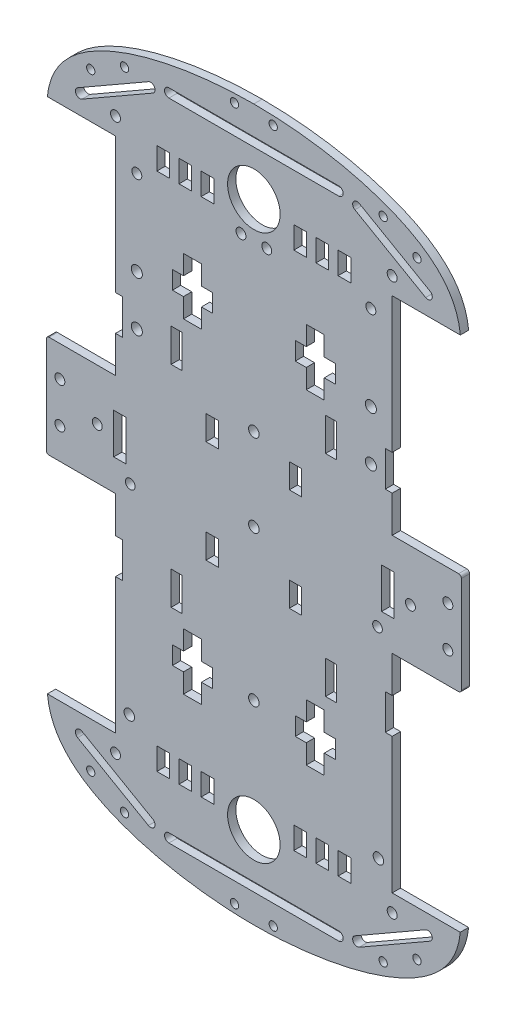
SolidWorks part; units mm, degrees
ref_plane "Plano frontal" through (0, 0, 0) normal (0, 0, 1) x (1, 0, 0)
ref_plane "Plano superior" through (0, 0, 0) normal (0, 1, 0) x (1, 0, 0)
ref_plane "Plano direito" through (0, 0, 0) normal (1, 0, 0) x (0, 0, -1)
sketch "Esboço1" plane through (0, 0, 0) normal (0, 0, 1) x (1, 0, 0)
  line L11 (217.8534, 118.1902) -> (156.4555, 118.1902)
  line L12 (156.4555, 114.9902) -> (217.8534, 114.9902)
  line L22 (125.058, 98.9462) -> (150.6447, 113.6322)
  line L23 (149.0517, 116.4076) -> (123.4651, 101.7215)
  line L52 (250.0473, -100.3339) -> (224.4607, -115.0199) construction
  line L53 (249.2509, -98.9462) -> (223.6642, -113.6322)
  line L54 (250.8438, -101.7215) -> (225.2572, -116.4076)
  line L55 (179.2694, -114.9902) -> (187.1544, -128.5) construction
  line L56 (222.205, -97.9605) -> (217.605, -97.9605)
  line L57 (222.205, -97.9605) -> (222.205, -89.9605)
  line L58 (222.205, -89.9605) -> (217.605, -89.9605)
  line L59 (217.605, -97.9605) -> (217.605, -89.9605)
  line L60 (214.205, -89.9605) -> (209.605, -89.9605)
  line L61 (214.205, -89.9605) -> (214.205, -97.9605)
  line L62 (214.205, -97.9605) -> (209.605, -97.9605)
  line L63 (209.605, -89.9605) -> (209.605, -97.9605)
  line L64 (206.205, -97.9605) -> (201.605, -97.9605)
  line L65 (206.205, -97.9605) -> (206.205, -89.9605)
  line L66 (206.205, -89.9605) -> (201.605, -89.9605)
  line L67 (201.605, -97.9605) -> (201.605, -89.9605)
  line L68 (206.0961, -68.9834) -> (212.5961, -68.9834)
  line L69 (206.0961, -68.9834) -> (206.0961, -48.4834)
  line L70 (206.0961, -48.4834) -> (212.5961, -48.4834)
  line L71 (212.5961, -68.9834) -> (212.5961, -48.4834)
  line L72 (202.1292, -55.4834) -> (216.5834, -55.4834)
  line L73 (202.1292, -55.4834) -> (202.1292, -61.9834)
  line L74 (202.1292, -61.9834) -> (216.5834, -61.9834)
  line L75 (216.5834, -55.4834) -> (216.5834, -61.9834)
  line L76 (213.0509, -44.0251) -> (217.0509, -44.0251)
  line L77 (213.0509, -44.0251) -> (213.0509, -32.0251)
  line L78 (213.0509, -32.0251) -> (217.0509, -32.0251)
  line L79 (217.0509, -44.0251) -> (217.0509, -32.0251)
  line L80 (199.9648, -22.9668) -> (204.4648, -22.9668)
  line L81 (199.9648, -22.9668) -> (199.9648, -14.1027)
  line L112 (137.1544, 44.4469) -> (139.6544, 44.4469)
  line L113 (139.6544, 44.4469) -> (139.6544, 31.679)
  line L114 (139.6544, 31.679) -> (137.1544, 31.679)
  line L115 (137.1544, 31.679) -> (137.1544, 18.463)
  line L116 (137.1544, 18.463) -> (113.1544, 18.463)
  line L117 (112.1544, 17.463) -> (112.1544, -17.463)
  line L118 (113.1544, -18.463) -> (137.1544, -18.463)
  line L119 (137.1544, -18.463) -> (137.1544, -31.679)
  line L120 (137.1544, -31.679) -> (139.6544, -31.679)
  line L121 (139.6544, -31.679) -> (139.6544, -44.4469)
  line L122 (139.6544, -44.4469) -> (137.1544, -44.4469)
  line L123 (137.1544, -44.4469) -> (137.1544, -93.463)
  line L124 (137.1544, -93.463) -> (112.5426, -93.463)
  line L125 (261.7663, -93.463) -> (237.1544, -93.463)
  line L126 (237.1544, -93.463) -> (237.1544, -44.4469)
  line L127 (237.1544, -44.4469) -> (234.6544, -44.4469)
  line L128 (234.6544, -44.4469) -> (234.6544, -31.679)
  line L129 (234.6544, -31.679) -> (237.1544, -31.679)
  line L130 (237.1544, -31.679) -> (237.1544, -18.463)
  line L131 (237.1544, -18.463) -> (261.1544, -18.463)
  line L132 (262.1544, -17.463) -> (262.1544, 17.463)
  line L133 (261.1544, 18.463) -> (237.1544, 18.463)
  line L134 (237.1544, 18.463) -> (237.1544, 31.679)
  line L135 (237.1544, 31.679) -> (234.6544, 31.679)
  line L136 (234.6544, 31.679) -> (234.6544, 44.4469)
  line L137 (234.6544, 44.4469) -> (237.1544, 44.4469)
  line L138 (237.1544, 44.4469) -> (237.1544, 93.463)
  line L139 (237.1544, 93.463) -> (261.7663, 93.463)
  line L140 (112.5426, 93.463) -> (137.1544, 93.463)
  line L141 (137.1544, 93.463) -> (137.1544, 44.4469)
  line L142 (199.9648, -14.1027) -> (204.4648, -14.1027)
  line L143 (204.4648, -22.9668) -> (204.4648, -14.1027)
  line L144 (233.296, -7.3) -> (237.796, -7.3)
  line L145 (201.605, -89.9605) -> (201.605, -97.9605)
  line L146 (206.205, -97.9605) -> (201.605, -97.9605)
  line L147 (206.205, -89.9605) -> (206.205, -97.9605)
  line L148 (206.205, -89.9605) -> (201.605, -89.9605)
  line L149 (209.605, -97.9605) -> (209.605, -89.9605)
  line L150 (214.205, -89.9605) -> (209.605, -89.9605)
  line L151 (214.205, -97.9605) -> (214.205, -89.9605)
  line L152 (214.205, -97.9605) -> (209.605, -97.9605)
  line L153 (217.605, -89.9605) -> (217.605, -97.9605)
  line L154 (222.205, -97.9605) -> (217.605, -97.9605)
  line L155 (222.205, -89.9605) -> (222.205, -97.9605)
  line L156 (222.205, -89.9605) -> (217.605, -89.9605)
  line L157 (237.796, 7.3) -> (237.796, -7.3)
  line L158 (233.296, -7.3) -> (237.796, -7.3)
  line L159 (233.296, 7.3) -> (233.296, -7.3)
  line L160 (233.296, 7.3) -> (237.796, 7.3)
  line L161 (204.4648, 22.9668) -> (204.4648, 14.1027)
  line L162 (199.9648, 14.1027) -> (204.4648, 14.1027)
  line L163 (199.9648, 22.9668) -> (199.9648, 14.1027)
  line L164 (199.9648, 22.9668) -> (204.4648, 22.9668)
  line L165 (217.0509, 44.0251) -> (217.0509, 32.0251)
  line L166 (213.0509, 32.0251) -> (217.0509, 32.0251)
  line L167 (213.0509, 44.0251) -> (213.0509, 32.0251)
  line L168 (213.0509, 44.0251) -> (217.0509, 44.0251)
  line L169 (216.5834, 55.4834) -> (216.5834, 61.9834)
  line L170 (202.1292, 61.9834) -> (216.5834, 61.9834)
  line L171 (202.1292, 55.4834) -> (202.1292, 61.9834)
  line L172 (202.1292, 55.4834) -> (216.5834, 55.4834)
  line L173 (212.5961, 68.9834) -> (212.5961, 48.4834)
  line L174 (206.0961, 48.4834) -> (212.5961, 48.4834)
  line L175 (206.0961, 68.9834) -> (206.0961, 48.4834)
  line L176 (206.0961, 68.9834) -> (212.5961, 68.9834)
  line L177 (201.605, 97.9605) -> (201.605, 89.9605)
  line L178 (206.205, 89.9605) -> (201.605, 89.9605)
  line L179 (206.205, 97.9605) -> (206.205, 89.9605)
  line L180 (206.205, 97.9605) -> (201.605, 97.9605)
  line L181 (209.605, 89.9605) -> (209.605, 97.9605)
  line L182 (214.205, 97.9605) -> (209.605, 97.9605)
  line L183 (214.205, 89.9605) -> (214.205, 97.9605)
  line L184 (214.205, 89.9605) -> (209.605, 89.9605)
  line L185 (217.605, 97.9605) -> (217.605, 89.9605)
  line L186 (222.205, 89.9605) -> (217.605, 89.9605)
  line L187 (222.205, 97.9605) -> (222.205, 89.9605)
  line L188 (222.205, 97.9605) -> (217.605, 97.9605)
  line L189 (237.1544, 93.463) -> (237.1544, 44.4469)
  line L190 (261.7663, 93.463) -> (237.1544, 93.463)
  line L191 (237.1544, -93.463) -> (261.7663, -93.463)
  line L192 (237.1544, -44.4469) -> (237.1544, -93.463)
  line L193 (234.6544, -44.4469) -> (237.1544, -44.4469)
  line L194 (234.6544, -31.679) -> (234.6544, -44.4469)
  line L195 (237.1544, -31.679) -> (234.6544, -31.679)
  line L196 (237.1544, -18.463) -> (237.1544, -31.679)
  line L197 (261.1544, -18.463) -> (237.1544, -18.463)
  line L198 (262.1544, 17.463) -> (262.1544, -17.463)
  line L199 (237.1544, 18.463) -> (261.1544, 18.463)
  line L200 (237.1544, 31.679) -> (237.1544, 18.463)
  line L201 (234.6544, 31.679) -> (237.1544, 31.679)
  line L202 (234.6544, 44.4469) -> (234.6544, 31.679)
  line L203 (237.1544, 44.4469) -> (234.6544, 44.4469)
  line L204 (225.2572, 116.4076) -> (250.8438, 101.7215)
  line L205 (249.2509, 98.9462) -> (223.6642, 113.6322)
  line L839 (124.2615, -100.3339) -> (149.8482, -115.0199) construction
  line L840 (152.1039, 97.9605) -> (156.7039, 97.9605)
  line L841 (152.1039, 97.9605) -> (152.1039, 89.9605)
  line L842 (152.1039, 89.9605) -> (156.7039, 89.9605)
  line L843 (156.7039, 97.9605) -> (156.7039, 89.9605)
  line L844 (160.1039, 89.9605) -> (164.7039, 89.9605)
  line L845 (160.1039, 89.9605) -> (160.1039, 97.9605)
  line L846 (160.1039, 97.9605) -> (164.7039, 97.9605)
  line L847 (164.7039, 89.9605) -> (164.7039, 97.9605)
  line L848 (168.1039, 97.9605) -> (172.7039, 97.9605)
  line L849 (168.1039, 97.9605) -> (168.1039, 89.9605)
  line L850 (168.1039, 89.9605) -> (172.7039, 89.9605)
  line L851 (172.7039, 97.9605) -> (172.7039, 89.9605)
  line L852 (168.2128, 68.9834) -> (161.7128, 68.9834)
  line L853 (168.2128, 68.9834) -> (168.2128, 48.4834)
  line L854 (168.2128, 48.4834) -> (161.7128, 48.4834)
  line L855 (161.7128, 68.9834) -> (161.7128, 48.4834)
  line L856 (172.1797, 55.4834) -> (157.7255, 55.4834)
  line L857 (172.1797, 55.4834) -> (172.1797, 61.9834)
  line L858 (172.1797, 61.9834) -> (157.7255, 61.9834)
  line L859 (157.7255, 55.4834) -> (157.7255, 61.9834)
  line L860 (161.2579, 44.0251) -> (157.2579, 44.0251)
  line L861 (161.2579, 44.0251) -> (161.2579, 32.0251)
  line L862 (161.2579, 32.0251) -> (157.2579, 32.0251)
  line L863 (157.2579, 44.0251) -> (157.2579, 32.0251)
  line L864 (174.344, 22.9668) -> (169.844, 22.9668)
  line L865 (174.344, 22.9668) -> (174.344, 14.1027)
  line L866 (174.344, 14.1027) -> (169.844, 14.1027)
  line L867 (169.844, 22.9668) -> (169.844, 14.1027)
  line L868 (141.0129, 7.3) -> (136.5129, 7.3)
  line L869 (141.0129, 7.3) -> (141.0129, -7.3)
  line L870 (141.0129, -7.3) -> (136.5129, -7.3)
  line L871 (136.5129, 7.3) -> (136.5129, -7.3)
  line L872 (152.1039, -89.9605) -> (156.7039, -89.9605)
  line L873 (152.1039, -89.9605) -> (152.1039, -97.9605)
  line L874 (152.1039, -97.9605) -> (156.7039, -97.9605)
  line L875 (156.7039, -89.9605) -> (156.7039, -97.9605)
  line L876 (160.1039, -97.9605) -> (164.7039, -97.9605)
  line L877 (160.1039, -97.9605) -> (160.1039, -89.9605)
  line L878 (160.1039, -89.9605) -> (164.7039, -89.9605)
  line L879 (164.7039, -97.9605) -> (164.7039, -89.9605)
  line L880 (168.1039, -89.9605) -> (172.7039, -89.9605)
  line L881 (168.1039, -89.9605) -> (168.1039, -97.9605)
  line L882 (168.1039, -97.9605) -> (172.7039, -97.9605)
  line L883 (172.7039, -89.9605) -> (172.7039, -97.9605)
  line L884 (125.058, -98.9462) -> (150.6447, -113.6322)
  line L885 (123.4651, -101.7215) -> (149.0517, -116.4076)
  line L887 (156.4555, -116.5902) -> (217.8534, -116.5902) construction
  line L888 (156.4555, -114.9902) -> (217.8534, -114.9902)
  line L889 (156.4555, -118.1902) -> (217.8534, -118.1902)
  line L891 (112.1544, 0) -> (262.1544, 0) construction
  line L894 (195.0395, -114.9902) -> (187.1544, -128.5) construction
  line L895 (187.1544, -128.5) -> (187.1544, 128.5) construction
  line L896 (141.0129, -7.3) -> (136.5129, -7.3)
  line L897 (169.844, -22.9668) -> (169.844, -14.1027)
  line L898 (174.344, -14.1027) -> (169.844, -14.1027)
  line L899 (174.344, -22.9668) -> (174.344, -14.1027)
  line L900 (174.344, -22.9668) -> (169.844, -22.9668)
  line L901 (157.2579, -44.0251) -> (157.2579, -32.0251)
  line L902 (161.2579, -32.0251) -> (157.2579, -32.0251)
  line L903 (161.2579, -44.0251) -> (161.2579, -32.0251)
  line L904 (161.2579, -44.0251) -> (157.2579, -44.0251)
  line L905 (157.7255, -55.4834) -> (157.7255, -61.9834)
  line L906 (172.1797, -61.9834) -> (157.7255, -61.9834)
  line L907 (172.1797, -55.4834) -> (172.1797, -61.9834)
  line L908 (172.1797, -55.4834) -> (157.7255, -55.4834)
  line L909 (161.7128, -68.9834) -> (161.7128, -48.4834)
  line L910 (168.2128, -48.4834) -> (161.7128, -48.4834)
  line L911 (168.2128, -68.9834) -> (168.2128, -48.4834)
  line L912 (168.2128, -68.9834) -> (161.7128, -68.9834)
  line L913 (172.7039, -97.9605) -> (172.7039, -89.9605)
  line L914 (168.1039, -89.9605) -> (172.7039, -89.9605)
  line L915 (168.1039, -97.9605) -> (168.1039, -89.9605)
  line L916 (168.1039, -97.9605) -> (172.7039, -97.9605)
  line L917 (164.7039, -89.9605) -> (164.7039, -97.9605)
  line L918 (160.1039, -97.9605) -> (164.7039, -97.9605)
  line L919 (160.1039, -89.9605) -> (160.1039, -97.9605)
  line L920 (160.1039, -89.9605) -> (164.7039, -89.9605)
  line L921 (156.7039, -97.9605) -> (156.7039, -89.9605)
  line L922 (152.1039, -89.9605) -> (156.7039, -89.9605)
  line L923 (152.1039, -97.9605) -> (152.1039, -89.9605)
  line L924 (152.1039, -97.9605) -> (156.7039, -97.9605)
  circle A7 centre (187.1544, 98.6872) radius 9.5
  arc A9 (217.8534, 114.9902) -> (217.8534, 118.1902) centre (217.8534, 116.5902) ccw
  arc A10 (156.4555, 118.1902) -> (156.4555, 114.9902) centre (156.4555, 116.5902) ccw
  arc A16 (123.4651, 101.7215) -> (125.058, 98.9462) centre (124.2615, 100.3339) ccw
  arc A17 (150.6447, 113.6322) -> (149.0517, 116.4076) centre (149.8482, 115.0199) ccw
  circle A19 centre (140.4106, 116.6652) radius 1.5
  circle A22 centre (180.1544, 125.3171) radius 1.5
  circle A25 centre (128.1982, 109.82) radius 1.5
  circle A28 centre (137.1601, 99.7255) radius 1.8
  circle A31 centre (144.8629, 85.6107) radius 1.8
  circle A34 centre (144.8595, 54.918) radius 2
  circle A37 centre (144.8575, 36.918) radius 2
  circle A40 centre (187.1544, 25.9492) radius 1.9
  circle A43 centre (182.4884, 85.6065) radius 1.8
  circle A46 centre (117.0478, 7.3) radius 1.8
  circle A49 centre (130.561, 0) radius 1.8
  circle A52 centre (142.4742, -12.7883) radius 1.75
  circle A55 centre (117.0478, -7.3) radius 1.8
  circle A58 centre (187.1544, -3.8693) radius 1.9
  arc A62 (249.2509, -98.9462) -> (250.8438, -101.7215) centre (250.0473, -100.3339) cw
  arc A63 (225.2572, -116.4076) -> (223.6642, -113.6322) centre (224.4607, -115.0199) cw
  circle A64 centre (237.1488, -99.7255) radius 1.8
  circle A65 centre (232.1814, -85.1446) radius 1.9
  arc A70 (113.1544, 18.463) -> (112.1544, 17.463) centre (113.1544, 17.463) ccw
  arc A71 (112.1544, -17.463) -> (113.1544, -18.463) centre (113.1544, -17.463) ccw
  arc A72 (261.1544, -18.463) -> (262.1544, -17.463) centre (261.1544, -17.463) ccw
  arc A73 (262.1544, 17.463) -> (261.1544, 18.463) centre (261.1544, 17.463) ccw
  circle A74 centre (194.1544, -125.3171) radius 1.5
  circle A75 centre (233.8982, -116.6652) radius 1.5
  circle A76 centre (246.1106, -109.82) radius 1.5
  arc A77 (262.1544, -17.463) -> (261.1544, -18.463) centre (261.1544, -17.463) cw
  arc A78 (261.1544, 18.463) -> (262.1544, 17.463) centre (261.1544, 17.463) cw
  circle A79 centre (257.2611, -7.3) radius 1.8
  circle A80 centre (231.8346, -12.7883) radius 1.75
  circle A81 centre (243.7479, 0) radius 1.8
  circle A82 centre (257.2611, 7.3) radius 1.8
  circle A83 centre (191.8205, 85.6065) radius 1.8
  circle A84 centre (229.4513, 36.918) radius 2
  circle A85 centre (229.4494, 54.918) radius 2
  circle A86 centre (229.446, 85.6107) radius 1.8
  circle A87 centre (237.1488, 99.7255) radius 1.8
  circle A88 centre (246.1106, 109.82) radius 1.5
  circle A89 centre (194.1544, 125.3171) radius 1.5
  circle A90 centre (233.8982, 116.6652) radius 1.5
  arc A91 (223.6642, 113.6322) -> (225.2572, 116.4076) centre (224.4607, 115.0199) cw
  arc A92 (250.8438, 101.7215) -> (249.2509, 98.9462) centre (250.0473, 100.3339) cw
  arc A93 (217.8534, 118.1902) -> (217.8534, 114.9902) centre (217.8534, 116.5902) cw
  arc A297 (125.058, -98.9462) -> (123.4651, -101.7215) centre (124.2615, -100.3339) ccw
  arc A298 (149.0517, -116.4076) -> (150.6447, -113.6322) centre (149.8482, -115.0199) ccw
  arc A299 (156.4555, -114.9902) -> (156.4555, -118.1902) centre (156.4555, -116.5902) ccw
  arc A300 (217.8534, -118.1902) -> (217.8534, -114.9902) centre (217.8534, -116.5902) ccw
  circle A304 centre (128.1982, -109.82) radius 1.5
  circle A307 centre (140.4106, -116.6652) radius 1.5
  circle A310 centre (180.1544, -125.3171) radius 1.5
  circle A313 centre (187.1544, -58.1845) radius 1.9
  circle A317 centre (142.1275, -85.1446) radius 1.9
  circle A318 centre (187.1544, -98.6872) radius 9.5
  circle A320 centre (137.1601, -99.7255) radius 1.8
  spline S4 degree 5 poles (187.1544, 128.5) (188.408, 128.5) (190.9307, 128.4741) (194.7617, 128.3573) (199.9592, 128.0441) (206.5738, 127.3774) (213.2552, 126.4175) (219.9321, 125.1438) (226.5128, 123.5365) (232.8831, 121.5815) (238.9087, 119.2734) (244.4485, 116.6114) (249.3672, 113.5981) (253.5492, 110.2389) (256.9152, 106.542) (259.4378, 102.5191) (260.7826, 99.0493) (261.4183, 96.3093) (261.6777, 94.4219) (261.7663, 93.463) knots 0 0 0 0 0 0 0.066667 0.133333 0.2 0.266667 0.333333 0.4 0.466667 0.533333 0.6 0.666667 0.733333 0.8 0.866667 0.933333 1 1 1 1 1 1 weights 1 1 1 1 1 1 1 1 1 1 1 1 1 1 1 1 1 1 1 1
  spline S5 degree 5 poles (261.7663, -93.463) (261.6777, -94.4219) (261.4183, -96.3093) (260.7826, -99.0493) (259.4378, -102.5191) (256.9152, -106.542) (253.5492, -110.2389) (249.3672, -113.5981) (244.4485, -116.6114) (238.9087, -119.2734) (232.8831, -121.5815) (226.5128, -123.5365) (219.9321, -125.1438) (213.2552, -126.4175) (206.5738, -127.3774) (199.9592, -128.0441) (194.7617, -128.3573) (190.9307, -128.4741) (188.408, -128.5) (187.1544, -128.5) knots 0 0 0 0 0 0 0.066667 0.133333 0.2 0.266667 0.333333 0.4 0.466667 0.533333 0.6 0.666667 0.733333 0.8 0.866667 0.933333 1 1 1 1 1 1 weights 1 1 1 1 1 1 1 1 1 1 1 1 1 1 1 1 1 1 1 1
  spline S12 degree 5 poles (112.5426, -93.463) (112.6312, -94.4219) (112.8905, -96.3093) (113.5263, -99.0493) (114.8711, -102.5191) (117.3937, -106.542) (120.7597, -110.2389) (124.9416, -113.5981) (129.8604, -116.6114) (135.4002, -119.2734) (141.4257, -121.5815) (147.7961, -123.5365) (154.3768, -125.1438) (161.0537, -126.4175) (167.735, -127.3774) (174.3497, -128.0441) (179.5472, -128.3573) (183.3782, -128.4741) (185.9009, -128.5) (187.1544, -128.5) knots 0 0 0 0 0 0 0.066667 0.133333 0.2 0.266667 0.333333 0.4 0.466667 0.533333 0.6 0.666667 0.733333 0.8 0.866667 0.933333 1 1 1 1 1 1 weights 1 1 1 1 1 1 1 1 1 1 1 1 1 1 1 1 1 1 1 1
  spline S13 degree 5 poles (187.1544, -128.5) (188.408, -128.5) (190.9307, -128.4741) (194.7617, -128.3573) (199.9592, -128.0441) (206.5738, -127.3774) (213.2552, -126.4175) (219.9321, -125.1438) (226.5128, -123.5365) (232.8831, -121.5815) (238.9087, -119.2734) (244.4485, -116.6114) (249.3672, -113.5981) (253.5492, -110.2389) (256.9152, -106.542) (259.4378, -102.5191) (260.7826, -99.0493) (261.4183, -96.3093) (261.6777, -94.4219) (261.7663, -93.463) knots 0 0 0 0 0 0 0.066667 0.133333 0.2 0.266667 0.333333 0.4 0.466667 0.533333 0.6 0.666667 0.733333 0.8 0.866667 0.933333 1 1 1 1 1 1 weights 1 1 1 1 1 1 1 1 1 1 1 1 1 1 1 1 1 1 1 1
  spline S14 degree 5 poles (261.7663, 93.463) (261.6777, 94.4219) (261.4183, 96.3093) (260.7826, 99.0493) (259.4378, 102.5191) (256.9152, 106.542) (253.5492, 110.2389) (249.3672, 113.5981) (244.4485, 116.6114) (238.9087, 119.2734) (232.8831, 121.5815) (226.5128, 123.5365) (219.9321, 125.1438) (213.2552, 126.4175) (206.5738, 127.3774) (199.9592, 128.0441) (194.7617, 128.3573) (190.9307, 128.4741) (188.408, 128.5) (187.1544, 128.5) knots 0 0 0 0 0 0 0.066667 0.133333 0.2 0.266667 0.333333 0.4 0.466667 0.533333 0.6 0.666667 0.733333 0.8 0.866667 0.933333 1 1 1 1 1 1 weights 1 1 1 1 1 1 1 1 1 1 1 1 1 1 1 1 1 1 1 1
  spline S15 degree 5 poles (187.1544, 128.5) (185.9009, 128.5) (183.3782, 128.4741) (179.5472, 128.3573) (174.3497, 128.0441) (167.735, 127.3774) (161.0537, 126.4175) (154.3768, 125.1438) (147.7961, 123.5365) (141.4257, 121.5815) (135.4002, 119.2734) (129.8604, 116.6114) (124.9416, 113.5981) (120.7597, 110.2389) (117.3937, 106.542) (114.8711, 102.5191) (113.5263, 99.0493) (112.8905, 96.3093) (112.6312, 94.4219) (112.5426, 93.463) knots 0 0 0 0 0 0 0.066667 0.133333 0.2 0.266667 0.333333 0.4 0.466667 0.533333 0.6 0.666667 0.733333 0.8 0.866667 0.933333 1 1 1 1 1 1 weights 1 1 1 1 1 1 1 1 1 1 1 1 1 1 1 1 1 1 1 1
  point P13 (0, 0)
  point P45 (137.0549, -107.6769)
  point P54 (187.1544, -116.5902)
  point P109 (237.254, -107.6769)
extrude "Ressalto-extrusão1" add sketch "Esboço1" along normal blind 3 contours S4 S15 L140 L141 L112 L113 L114 L115 L116 A70 L117 A71 L118 L119 L120 L121 L122 L123 L124 S12 S5 L125 L126 L127 L128 L129 L130 L131 A72 L132 A73 L133 L134 L135 L136 L137 L138 L139 A318 A317 A313 A310 A307 A304 region at (187.1544, -0.1269, 0)
